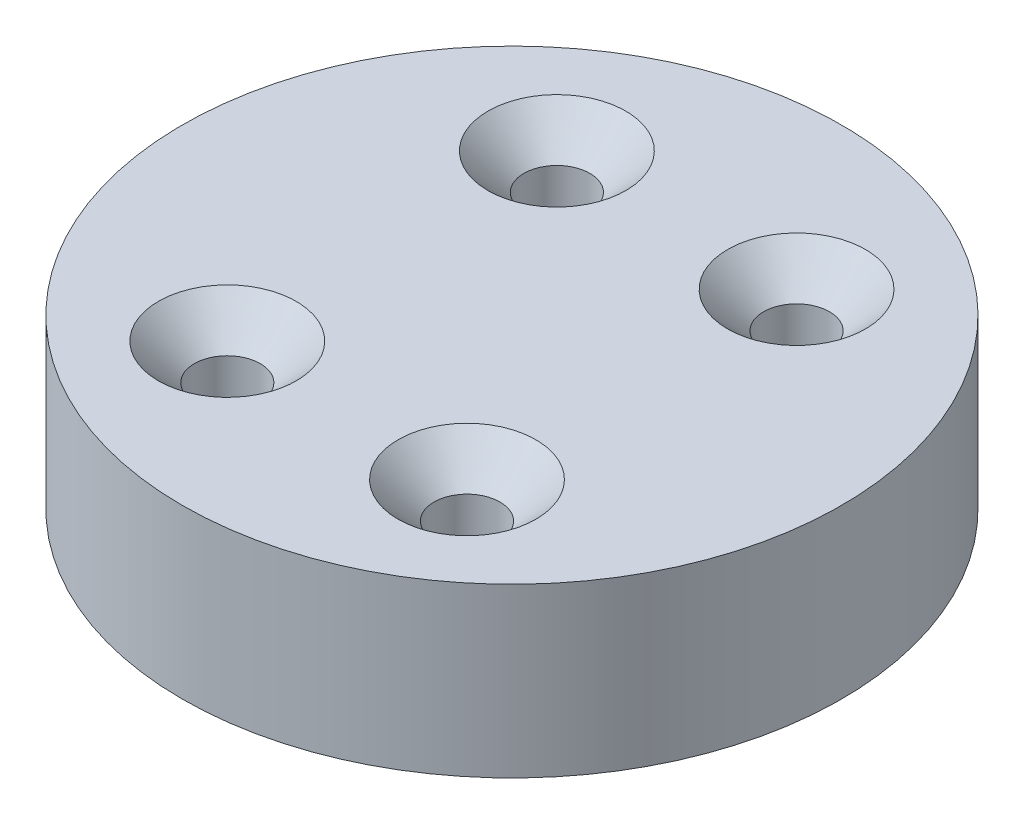
SolidWorks part; units mm, degrees
ref_plane "Front Plane" through (0, 0, 0) normal (0, 0, 1) x (1, 0, 0)
ref_plane "Top Plane" through (0, 0, 0) normal (0, 1, 0) x (1, 0, 0)
ref_plane "Right Plane" through (0, 0, 0) normal (1, 0, 0) x (0, 0, -1)
sketch "Sketch1" plane through (0, 0, 0) normal (0, 1, 0) x (1, 0, 0)
  line L0 (0, 0) -> (0, 68.5524) construction
  line L1 (0, 52.4907) -> (0, -49.3242) construction
  line L2 (10, -13.75) -> (10, 13.75)
  line L3 (10, -13.75) -> (-10, -13.75)
  line L4 (10, 13.75) -> (-10, 13.75)
  line L5 (-10, -13.75) -> (-10, 13.75)
  line L6 (10, -13.75) -> (-10, 13.75) construction
  line L7 (10, 13.75) -> (-10, -13.75) construction
  circle A0 centre (0, 0) radius 27.5
  circle A1 centre (-10, 13.75) radius 2.75
  circle A2 centre (10, 13.75) radius 2.75
  circle A3 centre (10, -13.75) radius 2.75
  circle A4 centre (-10, -13.75) radius 2.75
  dimension "D1" = 55
  dimension "D5" = 5.5
  dimension "D3" = 27.5
  dimension "D4" = 20
extrude "Boss-Extrude1" add sketch "Sketch1" along normal blind 14 contours A0 A4 L5 A1 L4 A2 L2 A3 L3 | A4 L3 A3 L2 A2 L4 A1 L5 region at (0, 0, 0) region at (-26.7222, 0, 0)
chamfer "Chamfer1" distance 3 angle 45 4 edges at (-10, 14, 16.5) (10, 14, 16.5) (10, 14, -11) (-10, 14, -11)
equation "\"LOGO_SIZE\"= 40"
equation "\"SECTION_SIZE\"= \"LOGO_SIZE\" / 6"
